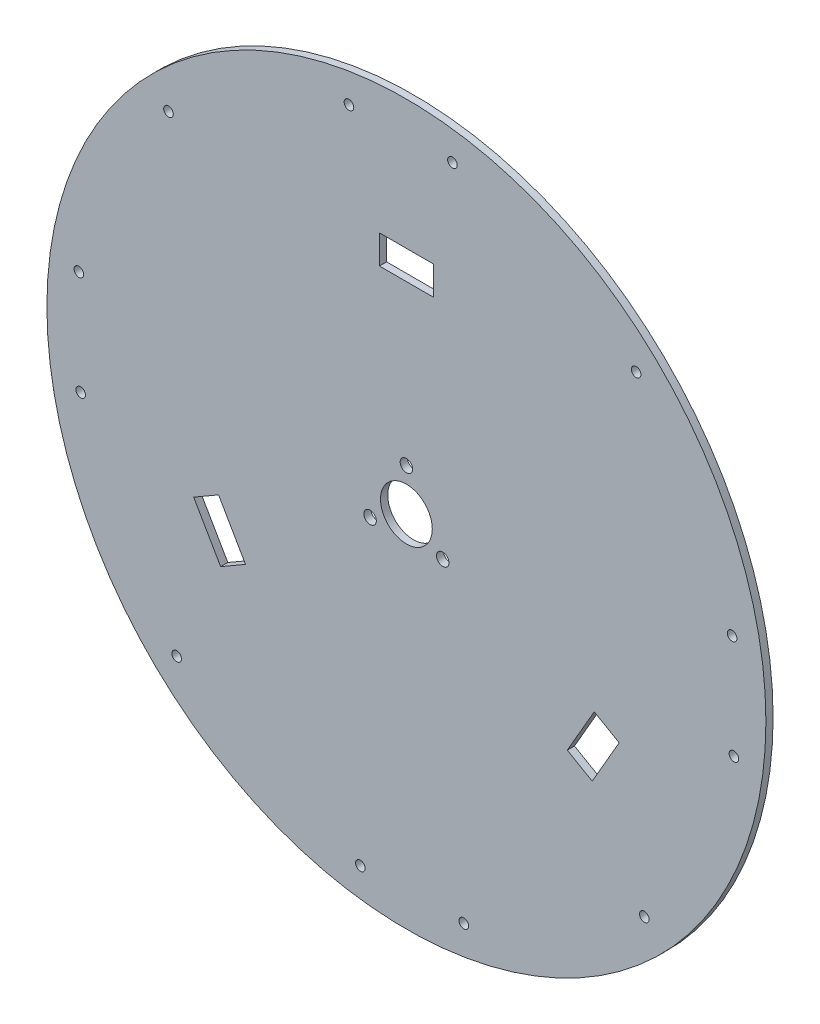
SolidWorks part; units mm, degrees
ref_plane "Alzado" through (0, 0, 0) normal (0, 0, 1) x (1, 0, 0)
ref_plane "Planta" through (0, 0, 0) normal (0, 1, 0) x (1, 0, 0)
ref_plane "Vista lateral" through (0, 0, 0) normal (1, 0, 0) x (0, 0, -1)
sketch "Croquis1" plane through (0, 0, 0) normal (0, 0, 1) x (1, 0, 0)
  line L0 (11.25, 96) -> (-11.25, 84) construction
  line L1 (-11.25, 96) -> (11.25, 96)
  line L2 (-11.25, 96) -> (-11.25, 84)
  line L3 (-11.25, 84) -> (11.25, 84)
  line L4 (11.25, 96) -> (11.25, 84)
  line L5 (-11.25, 96) -> (11.25, 84) construction
  line L6 (88.7634, -38.2572) -> (78.3711, -32.2572)
  line L7 (88.7634, -38.2572) -> (77.5134, -57.7428)
  line L8 (77.5134, -57.7428) -> (67.1211, -51.7428)
  line L9 (78.3711, -32.2572) -> (67.1211, -51.7428)
  line L10 (-77.5134, -57.7428) -> (-67.1211, -51.7428)
  line L11 (-77.5134, -57.7428) -> (-88.7634, -38.2572)
  line L12 (-88.7634, -38.2572) -> (-78.3711, -32.2572)
  line L13 (-67.1211, -51.7428) -> (-78.3711, -32.2572)
  circle A0 centre (0, 0) radius 150
  circle A1 centre (0, 0) radius 10.8
  circle A2 centre (0, 0) radius 90 construction
  circle A3 centre (0, 90) radius 40 construction
  circle A4 centre (77.9423, -45) radius 40 construction
  circle A5 centre (-77.9423, -45) radius 40 construction
  circle A6 centre (0, 0) radius 17.5 construction
  circle A7 centre (0, 17.5) radius 2.6
  circle A9 centre (15.1554, -8.75) radius 2.6
  circle A10 centre (-15.1554, -8.75) radius 2.6
  point P11 (0, 90)
  point P18 (0, 0)
  point P28 (0, 0)
  point P39 (0, 0)
  dimension "D1" = 300
  dimension "D2" = 21.6
  dimension "D3" = 180
  dimension "D4" = 80
  dimension "D9" = 5.2
  dimension "D10" = 3
  dimension "D5" = 12
  dimension "D6" = 22.5
  dimension "D7" = 3
  dimension "D8" = 3
extrude "Saliente-Extruir1" add sketch "Croquis1" along normal blind 3
sketch "Croquis2" plane through (0, 0, 3) normal (0, 0, 1) x (1, 0, 0)
  circle A0 centre (0, 0) radius 130
  circle A1 centre (0, 0) radius 150 construction
  dimension "D1" = 20
sketch "Croquis3" plane through (0, 0, 3) normal (0, 0, 1) x (1, 0, 0)
  circle A0 centre (-99.2689, 95.8629) radius 2
  circle A2 centre (-23.9634, 135.9035) radius 2
  circle A3 centre (19.2059, 136.657) radius 2
  circle A4 centre (95.8629, 99.2689) radius 2
  circle A5 centre (135.9035, 23.9634) radius 2
  circle A6 centre (136.657, -19.2059) radius 2
  circle A7 centre (99.2689, -95.8629) radius 2
  circle A8 centre (23.9634, -135.9035) radius 2
  circle A9 centre (-19.2059, -136.657) radius 2
  circle A10 centre (-95.8629, -99.2689) radius 2
  circle A11 centre (-135.9035, -23.9634) radius 2
  circle A12 centre (-136.657, 19.2059) radius 2
  dimension "D1" = 4
extrude "Cortar-Extruir1" cut sketch "Croquis3" against normal through all
